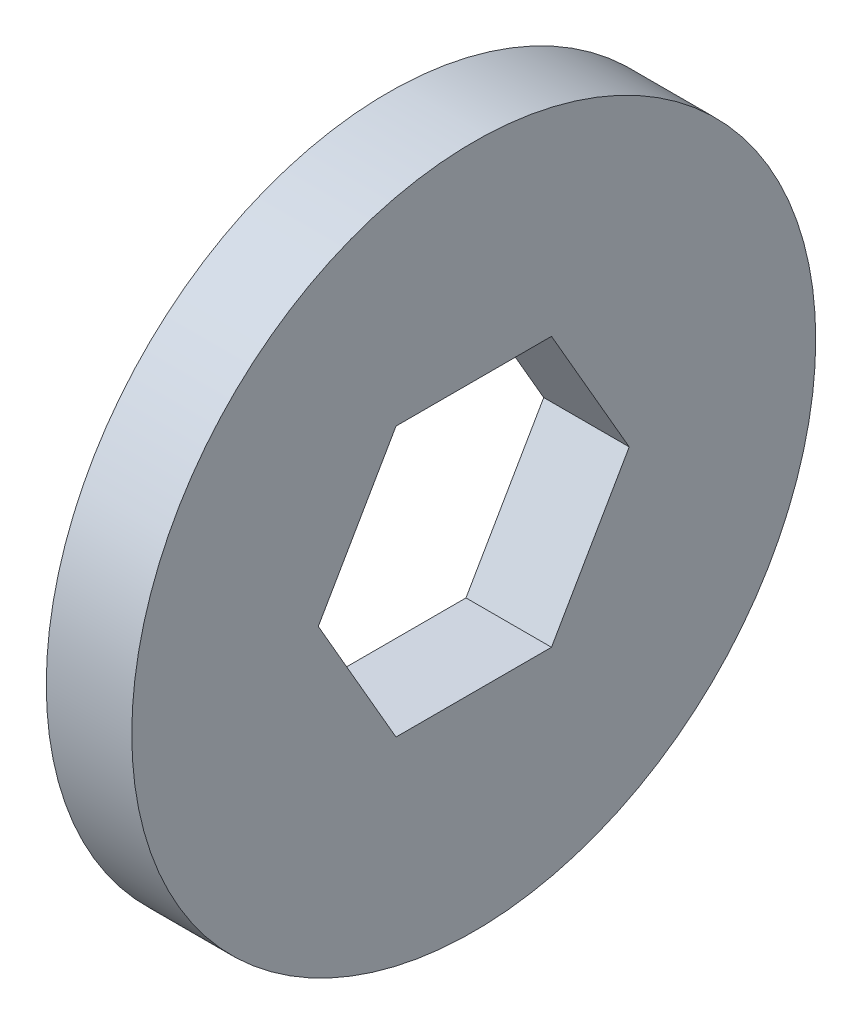
SolidWorks part; units mm, degrees
material "PET"
ref_plane "Front" through (0, 0, 0) normal (0, 0, 1) x (1, 0, 0)
ref_plane "Top" through (0, 0, 0) normal (0, 1, 0) x (1, 0, 0)
ref_plane "Right" through (0, 0, 0) normal (1, 0, 0) x (0, 0, -1)
sketch "Sketch1" plane through (0, 0, 0) normal (1, 0, 0) x (0, 0, -1)
  line L1 (2.8868, 0) -> (1.4434, 2.5)
  line L2 (1.4434, 2.5) -> (-1.4434, 2.5)
  line L3 (-1.4434, 2.5) -> (-2.8868, 0)
  line L4 (-2.8868, 0) -> (-1.4434, -2.5)
  line L5 (-1.4434, -2.5) -> (1.4434, -2.5)
  line L6 (1.4434, -2.5) -> (2.8868, 0)
  circle A0 centre (0, 0) radius 6.35
  circle A1 centre (0, 0) radius 2.5 construction
  dimension "D1" = 12.7
  dimension "D2" = 5
extrude "Boss-Extrude1" add sketch "Sketch1" along normal blind 1.5875
ref_axis "Axis1" through (1.5875, 0, 0) along (-1, 0, 0)
